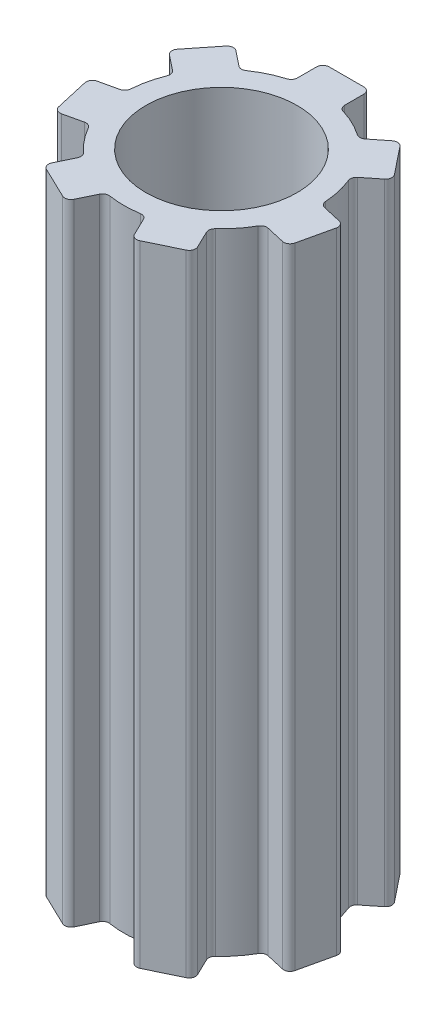
SolidWorks part; units mm, degrees
ref_plane "Front Plane" through (0, 0, 0) normal (0, 0, 1) x (1, 0, 0)
ref_plane "Top Plane" through (0, 0, 0) normal (0, 1, 0) x (1, 0, 0)
ref_plane "Right Plane" through (0, 0, 0) normal (1, 0, 0) x (0, 0, -1)
sketch "Sketch1" plane through (0, 0, 0) normal (0, 1, 0) x (1, 0, 0)
  circle A0 centre (0, 0) radius 3.937
  dimension "D1" = 7.874
extrude "Boss-Extrude1" add sketch "Sketch1" along normal blind 25.4
sketch "Sketch2" plane through (0, 25.4, 0) normal (0, 1, 0) x (1, 0, 0)
  line L0 (0, 0) -> (0, 8.3888) construction
  line L1 (-0.9525, 5.0392) -> (0.9525, 5.0392)
  line L2 (-0.9525, 5.0392) -> (-0.9525, 3.82)
  line L3 (-0.9525, 3.82) -> (0.9525, 3.82)
  line L4 (0.9525, 5.0392) -> (0.9525, 3.82)
  line L5 (-0.9525, 5.0392) -> (0.9525, 3.82) construction
  line L6 (-0.9525, 3.82) -> (0.9525, 5.0392) construction
  circle A1 centre (0, 0) radius 3.937 construction
  point P0 (0, 4.4296)
  dimension "D2" = 1.2192
  dimension "D3" = 1.905
extrude "Boss-Extrude2" add sketch "Sketch2" against normal up to surface (25.4 mm away) up to face at (0, 0, 3.937)
ref_axis "Axis1" through (0, 25.4, 0) along (0, -1, 0)
fillet "Fillet2" radius 0.254 4 edges at (0.9525, 12.7, -5.0392) (-0.9525, 12.7, -5.0392) (-0.9525, 12.7, -3.82) (0.9525, 12.7, -3.82)
pattern_circular "CirPattern4" count 7 over 360 about axis through (0, 25.4, 0) along (0, -1, 0) of "Fillet2", "Boss-Extrude2"
sketch "Sketch3" plane through (0, 25.4, 0) normal (0, 1, 0) x (1, 0, 0)
  circle A0 centre (0, 0) radius 3.048
  dimension "D1" = 6.096
extrude "Cut-Extrude1" cut sketch "Sketch3" against normal through all
